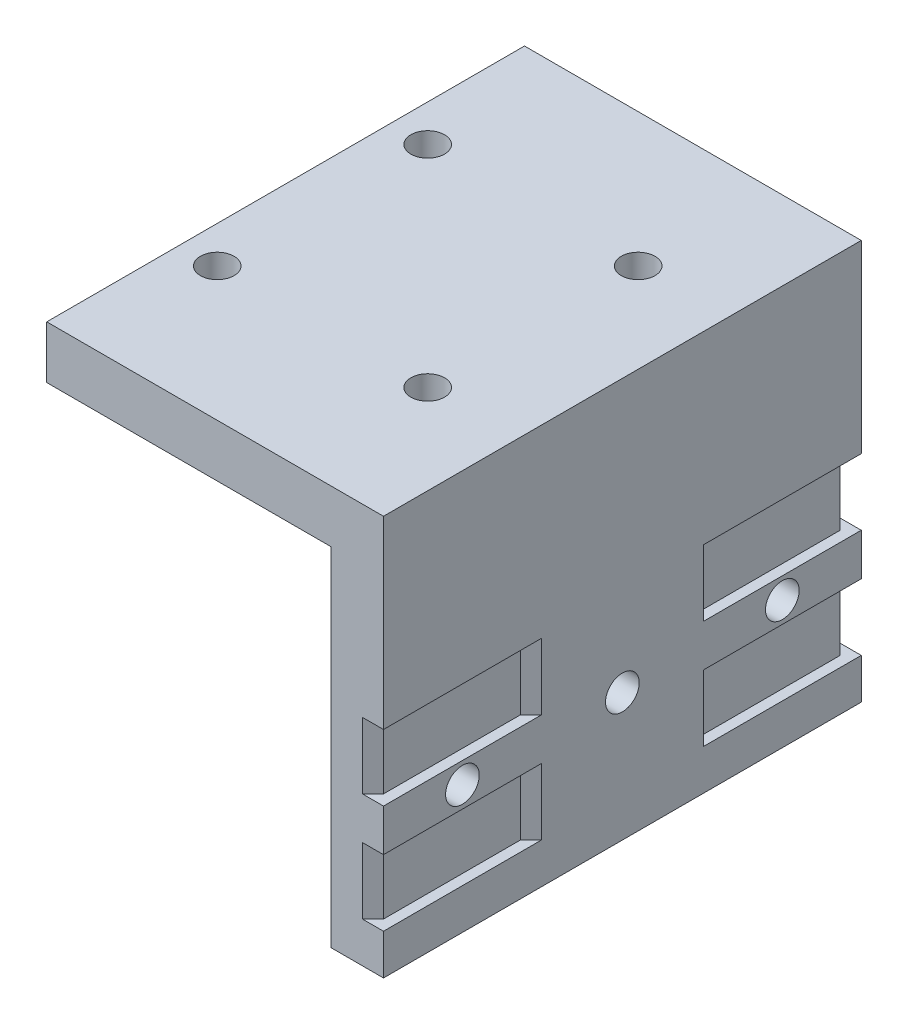
SolidWorks part; units mm, degrees
ref_plane "Front Plane" through (0, 0, 0) normal (0, 0, 1) x (1, 0, 0)
ref_plane "Top Plane" through (0, 0, 0) normal (0, 1, 0) x (1, 0, 0)
ref_plane "Right Plane" through (0, 0, 0) normal (1, 0, 0) x (0, 0, -1)
ref_plane "Rear Face Plane" through (30.8997, 0, 0) normal (1, 0, 0) x (0, 0, -1)
ref_plane "Clamp Thickness Plane" through (35.8997, 0, 0) normal (1, 0, 0) x (0, 0, -1)
ref_plane "Belt Clamp Cutout Thickness Plane" through (34.8997, 0, 0) normal (1, 0, 0) x (0, 0, -1)
sketch "Master Sketch" plane through (0, 0, 0) normal (1, 0, 0) x (0, 0, -1)
  line L0 (-9.6372, 31.8986) -> (-9.6372, 24.1486) construction
  line L1 (-55.0372, 20.8986) -> (-9.6372, 20.8986)
  line L2 (-55.0372, 20.8986) -> (-55.0372, 0.8986)
  line L3 (-55.0372, 0.8986) -> (-9.6372, 0.8986)
  line L4 (-9.6372, 20.8986) -> (-9.6372, 0.8986)
  line L5 (-55.0372, 31.8986) -> (-55.0372, 24.1486) construction
  line L6 (-9.6372, 31.8986) -> (-9.6372, 24.1486) construction
  line L7 (-55.0372, 31.8986) -> (-55.0372, 24.1486) construction
  line L8 (-9.6372, 23.8986) -> (-55.0372, 23.8986) construction
  line L9 (-9.6372, 23.8986) -> (-55.0372, 23.8986)
  line L10 (-48.5372, 33.8986) -> (-16.1372, 33.8986) construction
  line L11 (-48.5372, 33.8986) -> (-16.1372, 33.8986)
  dimension "D1" = 3
  dimension "D2" = 20
sketch "Main Block Sketch" plane through (30.8997, 0, 0) normal (1, 0, 0) x (0, 0, -1)
  line L1 (-55.0372, 0.8986) -> (-9.6372, 0.8986) construction
  line L3 (-55.0372, 38.8986) -> (-9.6372, 38.8986)
  line L5 (-55.0372, 0.8986) -> (-9.6372, 0.8986)
  line L8 (-55.0372, 33.8986) -> (-55.0372, 0.8986)
  line L12 (-9.6372, 38.8986) -> (-9.6372, 33.8986)
  line L13 (-55.0372, 38.8986) -> (-55.0372, 33.8986)
  line L14 (-9.6372, 33.8986) -> (-9.6372, 0.8986)
  point P0 (-9.6372, 33.8986)
  dimension "D1" = 5
extrude "Main Block" add sketch "Main Block Sketch" along normal up to surface (5 mm away) up to plane "Clamp Thickness Plane"
sketch "Belt Clamp Cutout Sketch" plane through (35.8997, 0, 0) normal (1, 0, 0) x (0, 0, -1)
  line L0 (-9.6372, 20.8986) -> (-9.6372, 0.8986) construction
  line L1 (-55.0372, 0.8986) -> (-9.6372, 0.8986) construction
  line L2 (-55.0372, 20.8986) -> (-55.0372, 0.8986) construction
  line L3 (-55.0372, 20.8986) -> (-9.6372, 20.8986) construction
  line L4 (-9.6372, 20.8986) -> (-9.6372, 0.8986) construction
  line L5 (-55.0372, 0.8986) -> (-9.6372, 0.8986) construction
  line L6 (-55.0372, 20.8986) -> (-55.0372, 0.8986) construction
  line L7 (-55.0372, 20.8986) -> (-9.6372, 20.8986) construction
  line L8 (-32.3372, 20.8986) -> (-32.3372, 0.8986) construction
  line L9 (-55.0372, 11.0486) -> (-40.0372, 11.0486)
  line L10 (-55.0372, 11.0486) -> (-55.0372, 4.7486)
  line L11 (-55.0372, 4.7486) -> (-40.0372, 4.7486)
  line L12 (-40.0372, 11.0486) -> (-40.0372, 4.7486)
  line L13 (-55.0372, 11.0486) -> (-40.0372, 4.7486) construction
  line L14 (-55.0372, 4.7486) -> (-40.0372, 11.0486) construction
  line L15 (-55.0372, 13.0486) -> (-8.7981, 13.0486) construction
  line L16 (-9.6372, 4.7486) -> (-24.6372, 11.0486) construction
  line L17 (-9.6372, 11.0486) -> (-24.6372, 4.7486) construction
  line L18 (-24.6372, 11.0486) -> (-24.6372, 4.7486)
  line L19 (-9.6372, 4.7486) -> (-24.6372, 4.7486)
  line L20 (-9.6372, 11.0486) -> (-9.6372, 4.7486)
  line L21 (-9.6372, 11.0486) -> (-24.6372, 11.0486)
  line L22 (-9.6372, 15.0486) -> (-24.6372, 21.3486) construction
  line L23 (-9.6372, 21.3486) -> (-24.6372, 15.0486) construction
  line L24 (-55.0372, 21.3486) -> (-40.0372, 15.0486) construction
  line L25 (-55.0372, 15.0486) -> (-40.0372, 21.3486) construction
  line L26 (-9.6372, 15.0486) -> (-24.6372, 15.0486)
  line L27 (-9.6372, 15.0486) -> (-9.6372, 21.3486)
  line L28 (-9.6372, 21.3486) -> (-24.6372, 21.3486)
  line L29 (-24.6372, 15.0486) -> (-24.6372, 21.3486)
  line L30 (-40.0372, 15.0486) -> (-40.0372, 21.3486)
  line L31 (-55.0372, 21.3486) -> (-40.0372, 21.3486)
  line L32 (-55.0372, 15.0486) -> (-55.0372, 21.3486)
  line L33 (-55.0372, 15.0486) -> (-40.0372, 15.0486)
  point P3 (-47.5372, 7.8986)
  point P17 (-17.1372, 7.8986)
  point P26 (-17.1372, 18.1986)
  point P27 (-47.5372, 18.1986)
  point P28 (-47.5372, 13.0486)
  point P29 (-17.1372, 13.0486)
  point P30 (-47.5372, 10.8986)
  point P31 (-17.1372, 10.8986)
  point P32 (-40.0372, 2.7486)
  point P33 (-40.0372, 12.7486)
  point P34 (-24.6372, 12.7486)
  point P35 (-32.3372, 0.8986)
  point P36 (0, 0)
  point P37 (0, 0)
  point P38 (0, 0)
  point P39 (-55.0372, 10.8986)
  point P40 (0, 0)
  point P41 (0, 0)
  point P42 (0, 0)
  point P43 (0, 0)
  point P44 (0, 0)
  dimension "D1" = 20
  dimension "D2" = 6.3
  dimension "D3" = 7
  dimension "D4" = 15
  dimension "D5" = 2
extrude "Belt Clamp Cutout" cut sketch "Belt Clamp Cutout Sketch" against normal up to surface (1 mm away) up to plane "Belt Clamp Cutout Thickness Plane"
hole_wizard "Belt Clamp Screw Holes" positions "Sketch3" profile "Sketch4" hole size "M3" standard "ISO" end condition through all
sketch "Sketch3" plane through (35.8997, 0, 0) normal (1, 0, 0) x (0, 0, -1)
  line L0 (-32.3372, 20.8986) -> (-32.3372, 0.8986) construction
  line L1 (-55.0372, 13.0486) -> (-8.7981, 13.0486) construction
  point P0 (-47.5372, 13.0486)
  point P3 (-17.1372, 13.0486)
  point P15 (-32.3372, 13.0486)
sketch "Sketch4" plane through (35.8997, 13.0486, 47.5372) normal (0, 1, 0) x (0, 0, -1)
  line L0 (0, 0) -> (0, 5)
  line L1 (0, 5) -> (1.6, 5)
  line L2 (1.6, 5) -> (1.6, 0)
  line L5 (1.6, 0) -> (0, 0)
  line L11 (0, -6.35) -> (0, 107.95) construction
  dimension "Thru Hole Dia." = 3.2
  dimension "Thru Hole Depth" = 5
sketch "Nut Trap Sketch" plane through (30.8997, 0, 0) normal (1, 0, 0) x (0, 0, -1)
  line L1 (-45.9784, 15.7486) -> (-49.0961, 15.7486)
  line L2 (-49.0961, 15.7486) -> (-50.6549, 13.0486)
  line L3 (-50.6549, 13.0486) -> (-49.0961, 10.3486)
  line L4 (-49.0961, 10.3486) -> (-45.9784, 10.3486)
  line L5 (-45.9784, 10.3486) -> (-44.4196, 13.0486)
  line L6 (-44.4196, 13.0486) -> (-45.9784, 15.7486)
  line L7 (-30.7784, 15.7486) -> (-33.8961, 15.7486)
  line L8 (-33.8961, 15.7486) -> (-35.4549, 13.0486)
  line L9 (-35.4549, 13.0486) -> (-33.8961, 10.3486)
  line L10 (-33.8961, 10.3486) -> (-30.7784, 10.3486)
  line L11 (-30.7784, 10.3486) -> (-29.2196, 13.0486)
  line L12 (-29.2196, 13.0486) -> (-30.7784, 15.7486)
  line L14 (-15.5784, 15.7486) -> (-18.6961, 15.7486)
  line L15 (-18.6961, 15.7486) -> (-20.2549, 13.0486)
  line L16 (-20.2549, 13.0486) -> (-18.6961, 10.3486)
  line L17 (-18.6961, 10.3486) -> (-15.5784, 10.3486)
  line L18 (-15.5784, 10.3486) -> (-14.0196, 13.0486)
  line L19 (-14.0196, 13.0486) -> (-15.5784, 15.7486)
  line L22 (-32.3372, 20.8986) -> (-32.3372, 0.8986) construction
  line L23 (-55.0372, 13.0486) -> (-8.7981, 13.0486) construction
  circle A0 centre (-47.5372, 13.0486) radius 2.7 construction
  circle A1 centre (-32.3372, 13.0486) radius 2.7 construction
  circle A2 centre (-17.1372, 13.0486) radius 2.7 construction
  point P10 (0, 0)
  point P18 (-31.9177, 12.0557)
  point P20 (-32.3372, 10.9057)
  point P29 (-32.3372, 12.0486)
  point P32 (0, 0)
  point P35 (-46.065, 14.7486)
  dimension "D1" = 5.4
extrude "Belt Clamp Screw Nut Traps" cut sketch "Nut Trap Sketch" along normal blind 2.3
chamfer "Belt Guide Chamfers" distance 1 angle 45 8 edges at (34.8997, 7.8986, 40.0372) (34.8997, 18.1986, 40.0372) (34.8997, 7.8986, 24.6372) (34.8997, 18.1986, 24.6372) (34.8997, 18.1986, 55.0372) (34.8997, 7.8986, 55.0372) (34.8997, 7.8986, 9.6372) (34.8997, 18.1986, 9.6372)
sketch "Rail Mount Block Sketch" plane through (30.8997, 0, 0) normal (1, 0, 0) x (0, 0, -1)
  line L2 (-55.0372, 38.8986) -> (-9.6372, 38.8986) construction
  line L4 (-55.0372, 38.8986) -> (-55.0372, 33.8986) construction
  line L5 (-55.0372, 38.8986) -> (-9.6372, 38.8986)
  line L7 (-55.0372, 38.8986) -> (-55.0372, 33.8986)
  line L8 (-55.0372, 33.8986) -> (-9.6372, 33.8986)
  line L9 (-9.6372, 33.8986) -> (-9.6372, 38.8986)
  point P1 (-9.6372, 33.8986)
  dimension "D1" = 5
extrude "Carriage Mounting Block" add sketch "Rail Mount Block Sketch" against normal up to surface (27 mm away)
sketch "Carriage Mounting Holes Position Sketch" plane through (0, 38.8986, 0) normal (0, 1, 0) x (1, 0, 0)
  line L0 (30.3997, -55.0372) -> (23.8997, -55.0372) construction
  line L1 (23.8997, -55.0372) -> (23.8997, -9.6372) construction
  line L2 (23.8997, -9.6372) -> (30.3997, -9.6372) construction
  line L3 (30.3997, -9.6372) -> (30.3997, -55.0372) construction
  line L4 (4.3997, -9.6372) -> (10.8997, -9.6372) construction
  line L5 (10.8997, -9.6372) -> (10.8997, -55.0372) construction
  line L6 (10.8997, -55.0372) -> (4.3997, -55.0372) construction
  line L7 (4.3997, -55.0372) -> (4.3997, -9.6372) construction
  line L8 (30.3997, -55.0372) -> (23.8997, -55.0372)
  line L9 (23.8997, -55.0372) -> (23.8997, -9.6372)
  line L10 (23.8997, -9.6372) -> (30.3997, -9.6372)
  line L11 (30.3997, -9.6372) -> (30.3997, -55.0372)
  line L12 (4.3997, -9.6372) -> (10.8997, -9.6372)
  line L13 (10.8997, -9.6372) -> (10.8997, -55.0372)
  line L14 (10.8997, -55.0372) -> (4.3997, -55.0372)
  line L15 (4.3997, -55.0372) -> (4.3997, -9.6372)
  circle A0 centre (7.3997, -42.3372) radius 1.25 construction
  circle A1 centre (27.3997, -42.3372) radius 1.25 construction
  circle A2 centre (27.3997, -22.3372) radius 1.25 construction
  circle A3 centre (7.3997, -22.3372) radius 1.25 construction
  circle A4 centre (7.3997, -42.3372) radius 1.25
  circle A5 centre (27.3997, -42.3372) radius 1.25
  circle A6 centre (27.3997, -22.3372) radius 1.25
  circle A7 centre (7.3997, -22.3372) radius 1.25
hole_wizard "Carriage Mounting Holes" positions "Sketch9" profile "Sketch10" hole size "M3" standard "ISO" end condition through all
sketch "Sketch9" plane through (0, 38.8986, 0) normal (0, 1, 0) x (1, 0, 0)
  point P0 (7.3997, -42.3372)
  point P3 (27.3997, -42.3372)
  point P6 (7.3997, -22.3372)
  point P9 (27.3997, -22.3372)
sketch "Sketch10" plane through (7.3997, 38.8986, 42.3372) normal (1, 0, 0) x (0, 0, 1)
  line L0 (0, 0) -> (0, 38)
  line L1 (0, 38) -> (1.6, 38)
  line L2 (1.6, 38) -> (1.6, 0)
  line L5 (1.6, 0) -> (0, 0)
  line L11 (0, -6.35) -> (0, 107.95) construction
  dimension "Thru Hole Dia." = 3.2
  dimension "Thru Hole Depth" = 38
